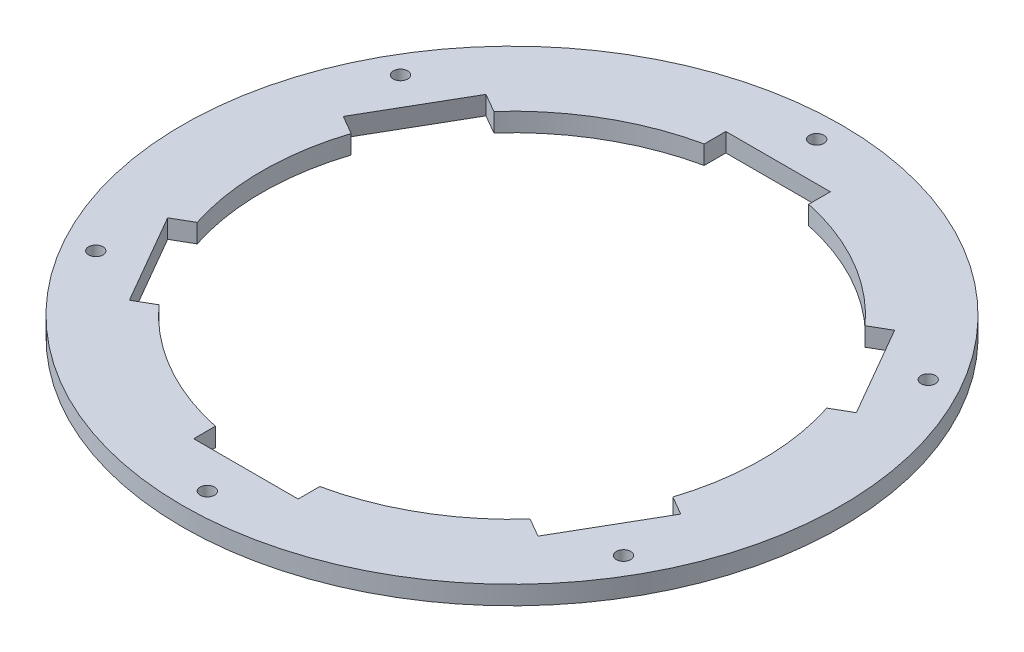
SolidWorks part; units mm, degrees
material "6061 Alloy"
ref_plane "Front Plane" through (0, 0, 0) normal (0, 0, 1) x (1, 0, 0)
ref_plane "Top Plane" through (0, 0, 0) normal (0, 1, 0) x (1, 0, 0)
ref_plane "Right Plane" through (0, 0, 0) normal (1, 0, 0) x (0, 0, -1)
sketch "Sketch1" plane through (0, 0, 0) normal (0, 1, 0) x (1, 0, 0)
  line L0 (-13.335, -62.4087) -> (-13.335, -66.2997)
  line L1 (13.335, -62.4087) -> (13.335, -66.2997)
  line L2 (-13.335, -67.9332) -> (13.335, -67.9332)
  line L3 (13.335, -66.2997) -> (13.335, -67.9332)
  line L4 (-13.335, -66.2997) -> (-13.335, -67.9332)
  circle A0 centre (0, 0) radius 63.8175
  circle A1 centre (0, 0) radius 84.1375
  circle A2 centre (0, 0) radius 67.6275
  circle A3 centre (0, -77.7875) radius 1.8288
  dimension "D1" = 127.635
  dimension "D2" = 168.275
  dimension "D8" = 3.6576
  dimension "D4" = 13.335
  dimension "D5" = 13.335
  dimension "D7" = 77.7875
  dimension "D6" = 5.5245
  dimension "D3" = 3.81
extrude "Boss-Extrude1" add sketch "Sketch1" along normal blind 4.7625 contours L1 A2 L0 A0 | A1 A2 A0 region at (-15.2384, 0, 64.3542) region at (-81.7577, 0, 0)
pattern_circular "CirPattern1" count 6 over 360 about axis through (0, 4.7625, 0) along (0, 1, 0) of face at (-13.335, 2.3813, 65.171) of face at (13.335, 2.3813, 65.171) of face at (0, 4.7625, 79.6163) of face at (0, 2.3813, 67.9332)
sketch "Sketch2" plane through (0, 0, 0) normal (1, 0, 0) x (0, 0, -1)
  line L0 (84.1375, 4.7625) -> (-84.1375, 4.7625) construction
  line L1 (-84.1375, 0) -> (84.1375, 0) construction
  line L2 (84.1375, 4.7625) -> (-84.1375, 4.7625)
  line L3 (-84.1375, 0) -> (84.1375, 0)
  line L4 (0, 0) -> (0, 4.7625) construction
  circle A0 centre (-83.2231, 0) radius 2.667
  dimension "D1" = 5.334
  dimension "D2" = 0.9144
revolve "Cut-Revolve1" [suppressed] cut sketch "Sketch2" angle 360 about L4
sketch "Sketch4" plane through (0, 0, 0) normal (0, -1, 0) x (1, 0, 0)
  line L0 (0, 0) -> (35.4013, -61.3168) construction
  line L1 (0, 0) -> (0, -39.7137) construction
  circle A0 centre (35.4013, -61.3168) radius 5.588
  dimension "D2" = 11.176
  dimension "D1" = 70.8025
  dimension "D3" = 30
extrude "Cut-Extrude1" cut sketch "Sketch4" against normal blind 1.905 contours A0 region at (35.4013, 0, -61.3168)
pattern_circular "CirPattern2" count 3 over 360 about axis through (0, 0, 0) along (0, 1, 0) of "Cut-Extrude1"
equation "\"Middle Coupler Inner Daimeter\"= 4.5in"
equation "\"Middle Coupler  Wall Thickness\" = 0.25in"
equation "\"Middle Coupler Bottom Thickness\"= 0.2in"
equation "\"Bearing Rail Offset\"= 0.45in"
equation "\"3-56 UNF Tap\"= 0.089in"
equation "\"3-56 UNF Clearance\"= 0.104in"
equation "\"Ball Bearing Distance\"= 0.03in"
equation "\"D1@Sketch1\"=\"Middle Coupler Inner Daimeter\"+0.5+0.0125*2in"
equation "\"TCA Outer Diameter\" = 6.625in"
equation "\"D2@Sketch1\"=\"TCA Outer Diameter\""
equation "\"D4@Sketch1\"=0.50 + (0.05/2)"
equation "\"D5@Sketch1\"=\"D4@Sketch1\""
equation "\"D7@Sketch1\"=(\"D2@Sketch1\"-0.5)/2"
equation "\"D8@Sketch1\"=\"6-32 Clearance\""
equation "\"D2@Sketch2\"=\"Interstage Aeroframe Wall Thickness\"/2"
equation "\"Interstage Aeroframe Wall Thickness\" = 0.072in"
equation "\"D1@Sketch4\"=((\"Middle Coupler Inner Daimeter\"+0.625in)/2in+0.225in)"
equation "\"Compression Spring OD\"= 0.42in"
equation "\"10-24 Tap\"= 0.157in"
equation "\"10-24 Clearance\"= 0.196in"
equation "\"D2@Sketch4\"=\"Compression Spring OD\"+0.02"
equation "\"D3@Sketch1\"=0.125in+(0.05/2)"
equation "\"Lower Stage Fuselage Wall Thickness\" = 0.25in"
equation "\"6-32 Tap\" = 0.107in"
equation "\"1/4-20 Tap\" = 0.201in"
equation "\"3-48 Tap\"= 0.079in"
equation "\"12-24 Tap\" = 0.177in"
equation "\"3-48 Clearance\" = 0.104in"
equation "\"6-32 Clearance\" = 0.144"
equation "\"D6@Sketch1\"=3/16 + 0.03"
